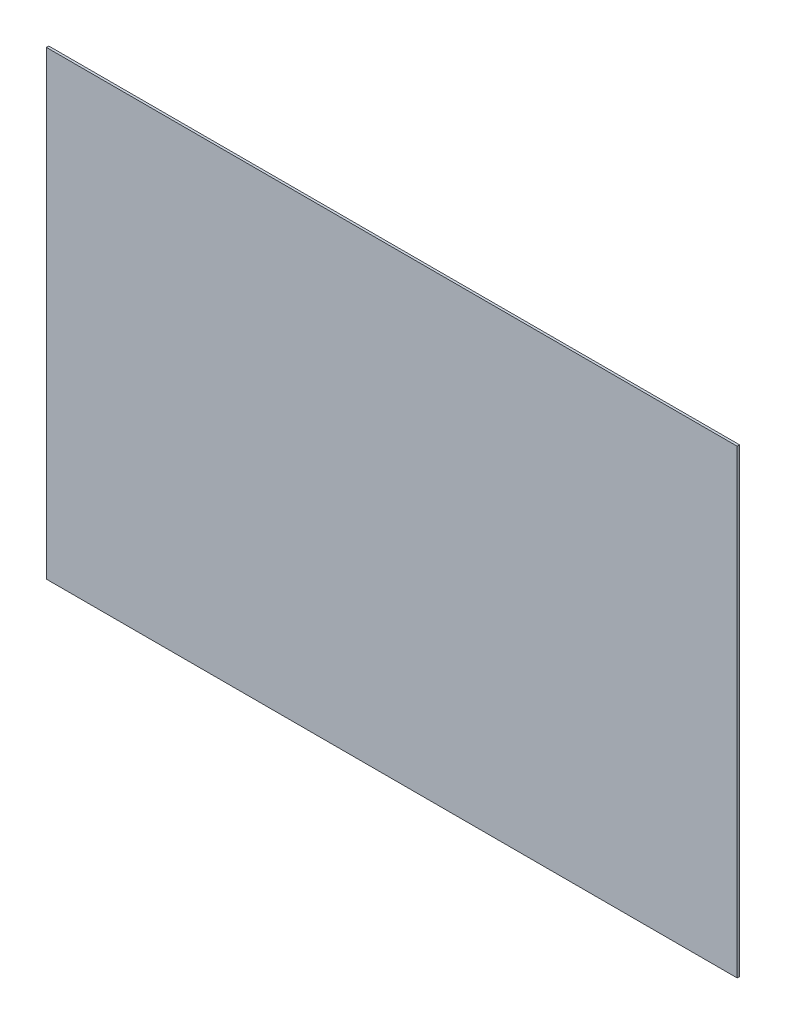
SolidWorks part; units mm, degrees
material "Acrylic (Medium-high impact)"
ref_plane "Front Plane" through (0, 0, 0) normal (0, 0, 1) x (1, 0, 0)
ref_plane "Top Plane" through (0, 0, 0) normal (0, 1, 0) x (1, 0, 0)
ref_plane "Right Plane" through (0, 0, 0) normal (1, 0, 0) x (0, 0, -1)
sketch "Sketch1" plane through (0, 0, 0) normal (0, 0, 1) x (1, 0, 0)
  line L0 (-457.2, 0) -> (457.2, 0)
  line L1 (-457.2, 0) -> (-457.2, 609.6)
  line L2 (-457.2, 609.6) -> (457.2, 609.6)
  line L3 (457.2, 609.6) -> (457.2, 0)
  point P4 (0, 0)
  dimension "D1" = 914.4
  dimension "D2" = 609.6
extrude "Boss-Extrude1" add sketch "Sketch1" against normal blind 3.175
